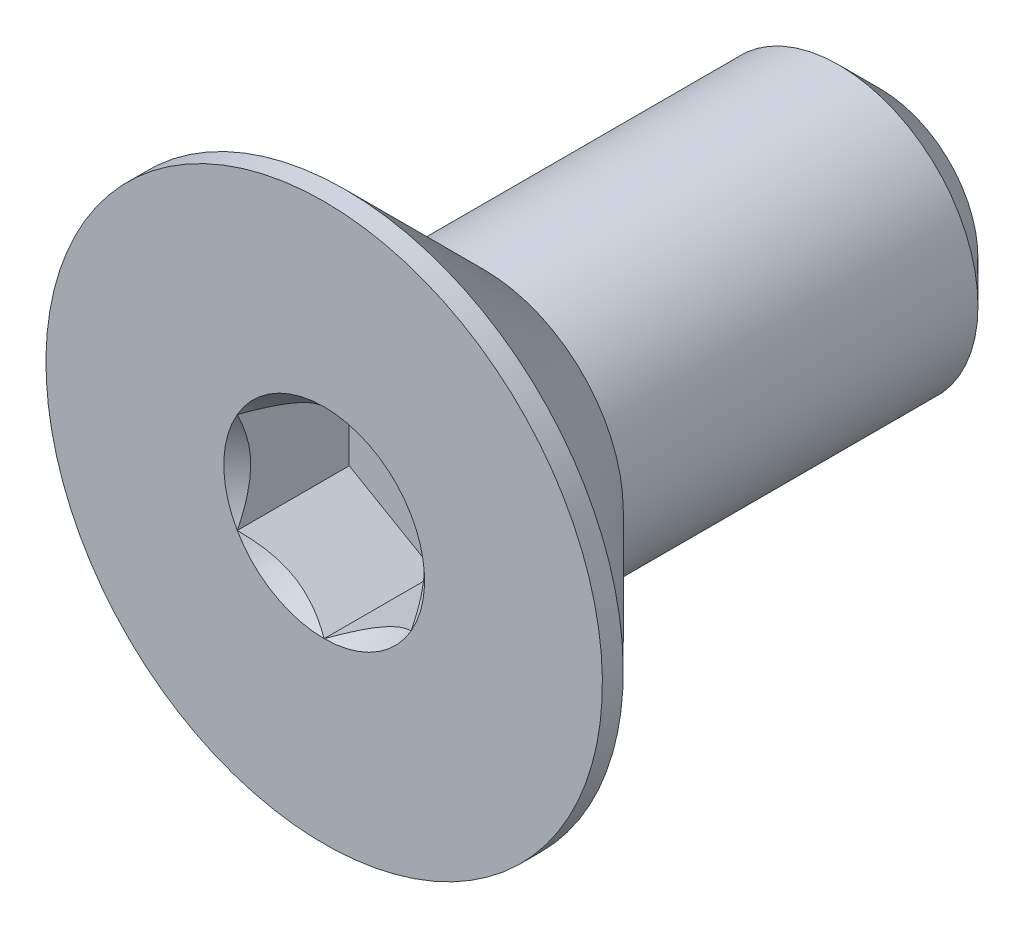
SolidWorks part; units mm, degrees
material "Alloy Steel"
ref_plane "Front" through (0, 0, 0) normal (0, 0, 1) x (1, 0, 0)
ref_plane "Top" through (0, 0, 0) normal (0, 1, 0) x (1, 0, 0)
ref_plane "Right" through (0, 0, 0) normal (1, 0, 0) x (0, 0, -1)
sketch "Sketch1" plane through (0, 0, 0) normal (1, 0, 0) x (0, 0, -1)
  line L0 (-4, 4) -> (-3.7, 4) construction
  line L1 (-3.7, 4) -> (-1.7, 2) construction
  line L2 (-4, 2) -> (4, 2) construction
  line L3 (4, 2) -> (4, 0) construction
  line L4 (4, 0) -> (-4, 0) construction
  line L5 (-4, 0) -> (-4, 4) construction
  line L6 (-4, 4) -> (-4, -4) construction
  line L7 (4, 2) -> (4, -2) construction
  line L8 (-4, -4) -> (-3.7, -4) construction
  line L9 (-3.7, -4) -> (-1.7, -2) construction
  line L11 (-4, 2) -> (-4, 0) construction
  line L12 (-1.7, 2) -> (-1.7, 0) construction
  line L13 (3.9563, 2.0758) -> (4.3063, 1.4696) construction
  line L14 (4.3063, 1.4696) -> (4.6563, 2.0758) construction
  line L15 (4.6563, 2.0758) -> (3.9563, 2.0758) construction
  line L16 (4.3063, 2.0758) -> (4.3063, 2) construction
  line L17 (4.3063, 2) -> (4.3063, 1.5453) construction
  line L18 (4.3063, 1.5453) -> (4.3063, 1.4696) construction
  line L19 (4.3063, 2.0379) -> (4.6344, 2.0379) construction
  line L20 (4.3063, 2.0379) -> (3.9781, 2.0379) construction
  line L21 (4, 2) -> (4.6125, 2) construction
  line L22 (4.2625, 1.5453) -> (4.35, 1.5453) construction
  line L23 (4, -2) -> (-1.7, -2) construction
  point P10 (2.25, -2)
  point P24 (-1.7, 2)
  point P30 (0, 0)
  dimension "Head Diameter" = 8
  dimension "Head Height" = 2.3
  dimension "Length" = 8
  dimension "Countersink Angle" = 90
  dimension "Thread Pitch" = 0.7
  dimension "D2" = 0.0875
  dimension "Minimum Thread Length" = 5.7
  dimension "Thread Size" = 4
  dimension "D1" = 1.75
sketch "Sketch2" plane through (0, 0, 0) normal (0, 0, 1) x (1, 0, 0)
  line L1 (0, 1.4434) -> (-1.25, 0.7217) construction
  line L2 (-1.25, 0.7217) -> (-1.25, -0.7217) construction
  line L3 (-1.25, -0.7217) -> (0, -1.4434) construction
  line L4 (0, -1.4434) -> (1.25, -0.7217) construction
  line L5 (1.25, -0.7217) -> (1.25, 0.7217) construction
  line L6 (1.25, 0.7217) -> (0, 1.4434) construction
  circle A0 centre (0, 0) radius 1.25 construction
  dimension "Drive Size" = 2.5
sketch "Sketch3" plane through (0, 0, 0) normal (1, 0, 0) x (0, 0, -1)
  line L0 (-4, 2) -> (4, 2)
  line L1 (4, 2) -> (4, 0)
  line L2 (4, 0) -> (-4, 0)
  line L3 (-4, 0) -> (-4, 2)
revolve "Revolve1" add sketch "Sketch3" angle 360 about L4
chamfer "Chamfer1" distance 0.6 angle 45 1 edges at (0, 2, -4)
sketch "Sketch6" plane through (0, 0, 0) normal (1, 0, 0) x (0, 0, -1)
  line L0 (-4, 4) -> (-3.7, 4)
  line L1 (-3.7, 4) -> (-1.7, 2)
  line L2 (-1.7, 2) -> (-1.7, 0)
  line L3 (-1.7, 0) -> (-4, 0)
  line L4 (-4, 0) -> (-4, 4)
revolve "Revolve2" add sketch "Sketch6" angle 360 about L4
sketch "Sketch8" plane through (0, 0, 4) normal (0, 0, 1) x (1, 0, 0)
  line L0 (0, 1.4434) -> (-1.25, 0.7217) construction
  line L1 (1.25, 0.7217) -> (0, 1.4434) construction
  line L2 (1.25, -0.7217) -> (1.25, 0.7217) construction
  line L3 (0, -1.4434) -> (1.25, -0.7217) construction
  line L4 (-1.25, 0.7217) -> (-1.25, -0.7217) construction
  line L5 (-1.25, -0.7217) -> (0, -1.4434) construction
  line L6 (0, 1.4434) -> (-1.25, 0.7217)
  line L7 (1.25, 0.7217) -> (0, 1.4434)
  line L8 (1.25, -0.7217) -> (1.25, 0.7217)
  line L9 (0, -1.4434) -> (1.25, -0.7217)
  line L10 (-1.25, 0.7217) -> (-1.25, -0.7217)
  line L11 (-1.25, -0.7217) -> (0, -1.4434)
extrude "Cut-Extrude1" cut sketch "Sketch8" against normal blind 1.61
sketch "Sketch9" plane through (0, 0, 4) normal (0, 0, 1) x (1, 0, 0)
  circle A0 centre (0, 0) radius 1.4434
extrude "Cut-Extrude2" cut sketch "Sketch9" against normal up to next (1.61 mm away) draft 45
ref_plane "Plane1" [suppressed] through (0, 0, 1.7) normal (0, 0, 1) x (1, 0, 0)
split "Split1" [suppressed] bodies to split 124
sketch "Sketch4" [suppressed] plane through (0, 0, -4) normal (0, 0, -1) x (-1, 0, 0)
  circle A0 centre (0, 0) radius 2 construction
  circle A1 centre (0, 0) radius 2
curve "Helix/Spiral1" [suppressed] pitch 0.7 height 6.4 turns 9.1429
sketch "Sketch10" [suppressed] plane through (0, 0, 0) normal (1, 0, 0) x (0, 0, -1)
  line L0 (3.9781, 2.0379) -> (4.6344, 2.0379)
  line L1 (4.6344, 2.0379) -> (4.35, 1.5453)
  line L2 (4.35, 1.5453) -> (4.2625, 1.5453)
  line L3 (4.2625, 1.5453) -> (3.9781, 2.0379)
sweep "Cut-Sweep1" [suppressed] cut profiles "Sketch10" path "Helix/Spiral1"
equation "\"D2@Sketch1\" = \"Thread Pitch@Sketch1\" / 8"
equation "\"D4@Helix/Spiral1\"=\"Thread Pitch@Sketch1\""
equation "\"D3@Helix/Spiral1\"=\"Minimum Thread Length@Sketch1\"+\"Thread Pitch@Sketch1\""
equation "\"D1@Chamfer1\"=\"Thread Size@Sketch1\"*.15"
equation "\"D1@Cut-Extrude1\"=\"Head Height@Sketch1\"*.7"
equation "\"D1@Sketch1\"=\"Thread Pitch@Sketch1\"*2.5"
